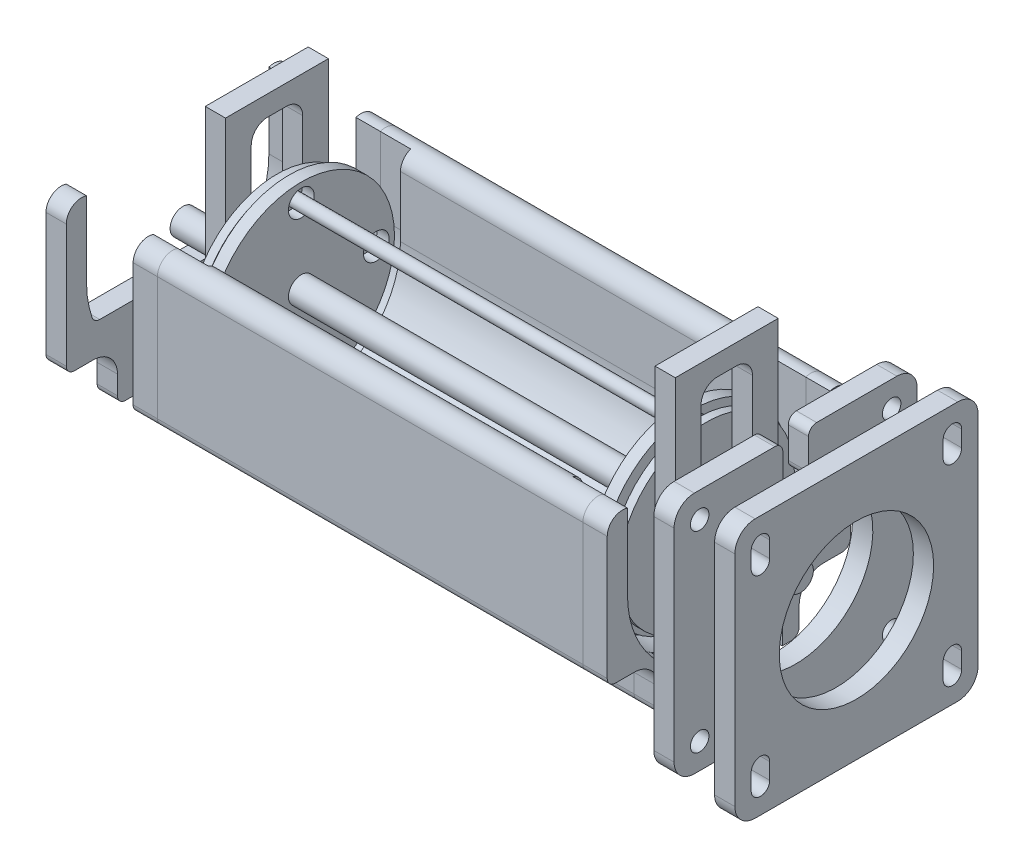
SolidWorks part; units mm, degrees
ref_plane "Front Plane" through (0, 0, 0) normal (0, 0, 1) x (1, 0, 0)
ref_plane "Top Plane" through (0, 0, 0) normal (0, 1, 0) x (1, 0, 0)
ref_plane "Right Plane" through (0, 0, 0) normal (1, 0, 0) x (0, 0, -1)
ref_plane "Plane1" through (-50, 0, 0) normal (1, 0, 0) x (0, 0, -1)
sketch "Sketch2" plane through (-50, 0, 0) normal (1, 0, 0) x (0, 0, -1)
  line L0 (0, 0) -> (0, 1.0694) construction
  circle A0 centre (0, 0) radius 3.175
  circle A1 centre (0, 18.5125) radius 1.5875 construction
  circle A2 centre (0, 18.5125) radius 3.175
  circle A3 centre (0, 0) radius 23
  circle A4 centre (-18.5125, 0) radius 1.5875 construction
  circle A5 centre (-18.5125, 0) radius 3.175
  circle A6 centre (0, -18.5125) radius 1.5875 construction
  circle A7 centre (0, -18.5125) radius 3.175
  circle A8 centre (18.5125, 0) radius 1.5875 construction
  circle A9 centre (18.5125, 0) radius 3.175
  dimension "D1" = 6.35
  dimension "D2" = 3.175
  dimension "D3" = 6.35
  dimension "D4" = 46
extrude "Boss-Extrude2" add sketch "Sketch2" along normal blind 3 separate body
ref_plane "Plane2" through (45, 0, 0) normal (1, 0, 0) x (0, 0, -1)
sketch "Sketch3" plane through (45, 0, 0) normal (1, 0, 0) x (0, 0, -1)
  line L0 (-22.4812, 0) -> (-22.4812, 15)
  line L1 (22.4812, 0) -> (22.4812, 15)
  line L2 (-23.371, -17.371) -> (-30, -17.371)
  line L3 (-30, 15) -> (-30, -17.371)
  line L4 (-17.371, -30) -> (17.371, -30)
  line L5 (-17.371, -23.371) -> (-17.371, -30)
  line L6 (17.371, -23.371) -> (17.371, -30)
  line L7 (23.371, -17.371) -> (30, -17.371)
  line L12 (30, -17.371) -> (30, 15)
  arc A0 (-22.4812, 0) -> (22.4812, 0) centre (0, 0) ccw
  arc A1 (-23.371, -17.371) -> (-17.371, -23.371) centre (-23.371, -23.371) cw
  arc A2 (17.371, -23.371) -> (23.371, -17.371) centre (23.371, -23.371) cw
  arc A3 (-30, 15) -> (-22.4812, 15) centre (-26.2406, 15) cw
  arc A4 (30, 15) -> (22.4812, 15) centre (26.2406, 15) ccw
  dimension "D1" = 6
  dimension "D2" = 6
extrude "Boss-Extrude3" add sketch "Sketch3" against normal blind 90 separate body
fillet "Fillet1" radius 2 4 edges at (0, -30, -17.371) (0, -30, 17.371) (0, -17.371, 30) (0, -17.371, -30)
ref_plane "Plane9" through (-51, 0, 0) normal (1, 0, 0) x (0, 0, -1)
sketch "Sketch16" plane through (-51, 0, 0) normal (1, 0, 0) x (0, 0, -1)
  circle A0 centre (0, 0) radius 21.6875
  circle A1 centre (0, 0) radius 3.175
  dimension "D1" = 6.35
extrude "Boss-Extrude7" add sketch "Sketch16" against normal blind 2 separate body
sketch "Sketch21" plane through (0, 0, 0) normal (1, 0, 0) x (0, 0, -1)
  circle A0 centre (-18.5125, 0) radius 1.5875
  circle A1 centre (0, 18.5125) radius 1.5875
  circle A2 centre (18.5125, 0) radius 1.5875
  circle A3 centre (0, -18.5125) radius 1.5875
  dimension "D1" = 4
extrude "Compression_Rods" add sketch "Sketch21" along normal mid plane 101.6 separate body
mirror "Mirror2" about plane through (0, 0, 0) normal (1, 0, 0) of bodies 102 113
ref_plane "Plane13" through (45, 0, 0) normal (1, 0, 0) x (0, 0, -1)
sketch "Sketch24" plane through (45, 0, 0) normal (1, 0, 0) x (0, 0, -1)
  line L0 (-25, 0) -> (-25, 18.5488)
  line L1 (25, 0) -> (25, 18.5488)
  line L2 (-23.371, -17.371) -> (-30, -17.371)
  line L3 (-30, 15) -> (-30, -17.371)
  line L4 (-17.371, -30) -> (17.371, -30)
  line L5 (-17.371, -23.371) -> (-17.371, -30)
  line L6 (17.371, -23.371) -> (17.371, -30)
  line L7 (23.371, -17.371) -> (30, -17.371)
  line L12 (30, -17.371) -> (30, 15)
  arc A0 (-25, 0) -> (25, 0) centre (0, 0) ccw
  arc A1 (-23.371, -17.371) -> (-17.371, -23.371) centre (-23.371, -23.371) cw
  arc A2 (17.371, -23.371) -> (23.371, -17.371) centre (23.371, -23.371) cw
  arc A3 (-30, 15) -> (-25, 18.5488) centre (-26.2406, 15) cw
  arc A4 (30, 15) -> (25, 18.5488) centre (26.2406, 15) ccw
  dimension "D1" = 6
  dimension "D2" = 6
extrude "Boss-Extrude13" add sketch "Sketch24" along normal blind 7.5 separate body
fillet "Fillet4" radius 2 4 edges at (48.75, -30, 17.371) (48.75, -17.371, 30) (48.75, -30, -17.371) (48.75, -17.371, -30)
ref_plane "Plane12" through (53, 0, 0) normal (1, 0, 0) x (0, 0, -1)
sketch "Sketch25" plane through (53, 0, 0) normal (1, 0, 0) x (0, 0, -1)
  line L0 (12.7, 0) -> (12.7, 40)
  line L1 (-12.7, 0) -> (-12.7, 40)
  line L3 (-12.7, 40) -> (12.7, 40)
  line L4 (12.7, 40) -> (12.5635, 39.8925)
  line L5 (6.35, 12) -> (6.35, 31)
  line L6 (-6.35, 12) -> (-6.35, 31)
  line L7 (2.35, 8) -> (-2.35, 8)
  line L9 (2.35, 35) -> (-2.35, 35)
  circle A0 centre (0, 0) radius 6.35
  arc A1 (12.7, 0) -> (-12.7, 0) centre (0, 0) cw
  arc A2 (6.35, 31) -> (2.35, 35) centre (2.35, 31) ccw
  arc A3 (-2.35, 35) -> (-6.35, 31) centre (-2.35, 31) ccw
  arc A4 (-6.35, 12) -> (-2.35, 8) centre (-2.35, 12) ccw
  arc A5 (6.35, 12) -> (2.35, 8) centre (2.35, 12) cw
  dimension "D1" = 4
  dimension "D3" = 12.7
  dimension "D2" = 25.4
  dimension "D4" = 19
extrude "Boss-Extrude14" add sketch "Sketch25" along normal blind 5 separate body contours A1 L0 L3 L1 A0 L5 A5 L7 A4 L6 A3 L9 A2 region at (53, -12.115, 0)
ref_plane "Plane14" through (52.5, 0, 0) normal (1, 0, 0) x (0, 0, -1)
sketch "Sketch26" plane through (52.5, 0, 0) normal (1, 0, 0) x (0, 0, -1)
  line L0 (-25, 0) -> (-25, 18.5488)
  line L1 (0, 0) -> (0, -46.298) construction
  line L2 (-23.371, -17.371) -> (-30, -17.371)
  line L3 (-30, 15) -> (-30, -17.371)
  line L4 (-17.371, -30) -> (-13.2, -30)
  line L5 (-17.371, -23.371) -> (-17.371, -30)
  line L6 (13.2, -30) -> (13.2, -21.2311)
  line L7 (17.371, -23.371) -> (17.371, -30)
  line L8 (17.371, -30) -> (13.2, -30)
  line L10 (30, 15) -> (30, -17.371)
  line L11 (23.371, -17.371) -> (30, -17.371)
  line L12 (25, 0) -> (25, 18.5488)
  line L15 (-13.2, -30) -> (-13.2, -21.2311)
  arc A0 (-25, 0) -> (-13.2, -21.2311) centre (0, 0) ccw
  arc A1 (-23.371, -17.371) -> (-17.371, -23.371) centre (-23.371, -23.371) cw
  arc A2 (30, 15) -> (25, 18.5488) centre (26.2406, 15) ccw
  arc A3 (-30, 15) -> (-25, 18.5488) centre (-26.2406, 15) cw
  arc A4 (23.371, -17.371) -> (17.371, -23.371) centre (23.371, -23.371) ccw
  arc A5 (25, 0) -> (13.2, -21.2311) centre (0, 0) cw
  dimension "D1" = 6
extrude "Boss-Extrude15" add sketch "Sketch26" along normal blind 6 separate body
ref_plane "Plane15" through (70, 0, 0) normal (1, 0, 0) x (0, 0, -1)
sketch "Sketch27" plane through (70, 0, 0) normal (1, 0, 0) x (0, 0, -1)
  line L0 (-5.175, 30) -> (-25, 30)
  line L1 (23.6855, -23.6855) -> (-23.6855, -23.6855) construction
  line L2 (23.6855, -23.6855) -> (23.6855, 23.6855) construction
  line L3 (23.6855, 23.6855) -> (-23.6855, 23.6855) construction
  line L4 (-23.6855, -23.6855) -> (-23.6855, 23.6855) construction
  line L5 (23.6855, -23.6855) -> (-23.6855, 23.6855) construction
  line L6 (23.6855, 23.6855) -> (-23.6855, -23.6855) construction
  line L7 (5.175, 30) -> (25, 30)
  line L8 (-30, 25) -> (-30, -25)
  line L9 (-25, -30) -> (25, -30)
  line L10 (30, 25) -> (30, -25)
  line L11 (-30, 30) -> (30, -30) construction
  line L12 (-30, -30) -> (30, 30) construction
  line L13 (-3.175, 28) -> (-3.175, 20.404)
  line L14 (3.175, 28) -> (3.175, 20.404)
  line L15 (0, 0) -> (0, 18.7836) construction
  circle A0 centre (-23.6855, 23.6855) radius 2.286
  circle A1 centre (23.6855, 23.6855) radius 2.286
  circle A2 centre (-23.6855, -23.6855) radius 2.286
  circle A3 centre (23.6855, -23.6855) radius 2.286
  arc A4 (-19.05, 0) -> (19.05, 0) centre (0, 0) ccw
  arc A5 (-30, -25) -> (-25, -30) centre (-25, -25) ccw
  arc A6 (25, -30) -> (30, -25) centre (25, -25) ccw
  arc A7 (30, 25) -> (25, 30) centre (25, 25) ccw
  arc A8 (-30, 25) -> (-25, 30) centre (-25, 25) cw
  arc A9 (-19.05, 0) -> (-4.6833, 18.4653) centre (0, 0) cw
  arc A10 (19.05, 0) -> (4.6833, 18.4653) centre (0, 0) ccw
  arc A11 (-3.175, 20.404) -> (-4.6833, 18.4653) centre (-5.175, 20.404) cw
  arc A12 (3.175, 20.404) -> (4.6833, 18.4653) centre (5.175, 20.404) ccw
  arc A13 (3.175, 28) -> (5.175, 30) centre (5.175, 28) cw
  arc A14 (-3.175, 28) -> (-5.175, 30) centre (-5.175, 28) ccw
  point P0 (0, 0)
  point P10 (0, 0)
  point P37 (-3.175, 18.7836)
  point P40 (3.175, 18.7836)
  dimension "D3" = 5
  dimension "D1" = 2
  dimension "D2" = 60
  dimension "D5" = 60
extrude "Boss-Extrude17" add sketch "Sketch27" along normal blind 5 separate body
fillet "Fillet7" radius 2 2 edges at (55.5, -30, 17.371) (55.5, -17.371, 30)
fillet "Fillet8" radius 2 2 edges at (55.5, -30, -17.371) (55.5, -17.371, -30)
mirror "Mirror5" about plane through (0, 0, 0) normal (1, 0, 0) of bodies 127
mirror "Mirror6" about plane through (0, 0, 0) normal (1, 0, 0) of bodies 129 130
mirror "Mirror8" about plane through (0, 0, 0) normal (1, 0, 0) of bodies 128
sketch "Sketch28" plane through (0, 0, 0) normal (1, 0, 0) x (0, 0, -1)
  circle A0 centre (0, 0) radius 3.175
extrude "Boss-Extrude19" add sketch "Sketch28" along normal mid plane 152.4
ref_plane "Plane16" through (85, 0, 0) normal (1, 0, 0) x (0, 0, -1)
sketch "Sketch30" plane through (85, 0, 0) normal (1, 0, 0) x (0, 0, -1)
  line L0 (-25.9715, 25.6855) -> (-25.9715, 21.6855)
  line L1 (23.6855, -23.6855) -> (-23.6855, -23.6855) construction
  line L2 (23.6855, -23.6855) -> (23.6855, 23.6855) construction
  line L3 (23.6855, 23.6855) -> (-23.6855, 23.6855) construction
  line L4 (-23.6855, -23.6855) -> (-23.6855, 23.6855) construction
  line L5 (23.6855, -23.6855) -> (-23.6855, 23.6855) construction
  line L6 (23.6855, 23.6855) -> (-23.6855, -23.6855) construction
  line L7 (-25, 32) -> (25, 32)
  line L8 (-30, 27) -> (-30, -27)
  line L9 (-25, -32) -> (25, -32)
  line L10 (30, 27) -> (30, -27)
  line L11 (-30, 32) -> (30, -32) construction
  line L12 (-30, -32) -> (30, 32) construction
  line L13 (-21.3995, 25.6855) -> (-21.3995, 21.6855)
  line L14 (21.3995, 25.6855) -> (21.3995, 21.6855)
  line L16 (25.9715, 25.6855) -> (25.9715, 21.6855)
  line L18 (25.9715, -25.6855) -> (25.9715, -21.6855)
  line L19 (21.3995, -25.6855) -> (21.3995, -21.6855)
  line L20 (-21.3995, -25.6855) -> (-21.3995, -21.6855)
  line L21 (-25.9715, -25.6855) -> (-25.9715, -21.6855)
  arc A0 (25.9715, 25.6855) -> (21.3995, 25.6855) centre (23.6855, 25.6855) ccw
  arc A1 (25.9715, 21.6855) -> (21.3995, 21.6855) centre (23.6855, 21.6855) cw
  arc A2 (25.9715, -21.6855) -> (21.3995, -21.6855) centre (23.6855, -21.6855) ccw
  arc A3 (25.9715, -25.6855) -> (21.3995, -25.6855) centre (23.6855, -25.6855) cw
  arc A4 (-25.9715, 25.6855) -> (-21.3995, 25.6855) centre (-23.6855, 25.6855) cw
  arc A5 (-25, 32) -> (-30, 27) centre (-25, 27) ccw
  arc A6 (-30, -27) -> (-25, -32) centre (-25, -27) ccw
  arc A7 (25, -32) -> (30, -27) centre (25, -27) ccw
  arc A8 (25, 32) -> (30, 27) centre (25, 27) cw
  circle A9 centre (0, 0) radius 19.05
  arc A10 (-25.9715, 21.6855) -> (-21.3995, 21.6855) centre (-23.6855, 21.6855) ccw
  arc A11 (-25.9715, -21.6855) -> (-21.3995, -21.6855) centre (-23.6855, -21.6855) cw
  arc A12 (-25.9715, -25.6855) -> (-21.3995, -25.6855) centre (-23.6855, -25.6855) ccw
  point P0 (0, 0)
  point P10 (0, 0)
  dimension "D3" = 5
  dimension "D1" = 5
  dimension "D2" = 60
  dimension "D5" = 64
extrude "Boss-Extrude21" add sketch "Sketch30" along normal blind 5 separate body
ref_plane "Plane17" through (-75, 0, 0) normal (1, 0, 0) x (0, 0, -1)
sketch "Sketch34" plane through (-75, 0, 0) normal (1, 0, 0) x (0, 0, -1)
  line L0 (-25, 0) -> (-25, 18.5488)
  line L1 (25, 0) -> (25, 18.5488)
  line L2 (-23.371, -17.371) -> (-28, -17.371)
  line L3 (-30, 15) -> (-30, -15.371)
  line L4 (-15.371, -30) -> (15.371, -30)
  line L5 (-17.371, -23.371) -> (-17.371, -28)
  line L6 (17.371, -23.371) -> (17.371, -28)
  line L7 (23.371, -17.371) -> (28, -17.371)
  line L8 (21.7342, -9.525) -> (-21.7342, -9.525)
  line L9 (0, 0) -> (0, -13.7519) construction
  line L12 (30, -15.371) -> (30, 15)
  arc A0 (23.6241, -8.1793) -> (25, 0) centre (0, 0) ccw
  arc A1 (-23.371, -17.371) -> (-17.371, -23.371) centre (-23.371, -23.371) cw
  arc A2 (17.371, -23.371) -> (23.371, -17.371) centre (23.371, -23.371) cw
  arc A3 (-30, 15) -> (-25, 18.5488) centre (-26.2406, 15) cw
  arc A4 (30, 15) -> (25, 18.5488) centre (26.2406, 15) ccw
  arc A5 (-23.6241, -8.1793) -> (-21.7342, -9.525) centre (-21.7342, -7.525) ccw
  arc A6 (-23.6241, -8.1793) -> (-25, 0) centre (0, 0) cw
  arc A7 (-28, -17.371) -> (-30, -15.371) centre (-28, -15.371) cw
  arc A8 (23.6241, -8.1793) -> (21.7342, -9.525) centre (21.7342, -7.525) cw
  arc A9 (-17.371, -28) -> (-15.371, -30) centre (-15.371, -28) ccw
  arc A10 (17.371, -28) -> (15.371, -30) centre (15.371, -28) cw
  arc A11 (28, -17.371) -> (30, -15.371) centre (28, -15.371) ccw
  dimension "D1" = 6
  dimension "D2" = 6
  dimension "D3" = 2
  dimension "D4" = 2
extrude "Boss-Extrude22" add sketch "Sketch34" against normal blind 5 separate body
ref_axis "Axis2" through (98.5, 0, 0) along (-1, 0, 0)
